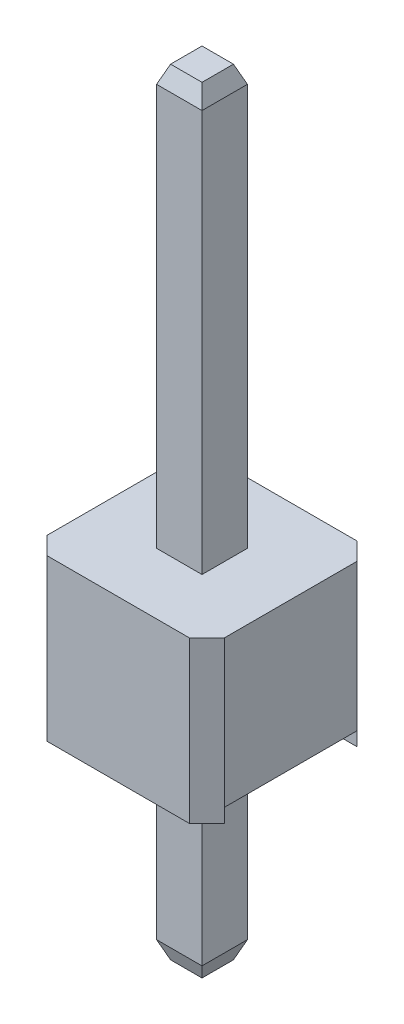
SolidWorks part; units mm, degrees
ref_plane "Front Plane" through (0, 0, 0) normal (0, 0, 1) x (1, 0, 0)
ref_plane "Top Plane" through (0, 0, 0) normal (0, 1, 0) x (1, 0, 0)
ref_plane "Right Plane" through (0, 0, 0) normal (1, 0, 0) x (0, 0, -1)
sketch "Sketch1" plane through (0, 0, 0) normal (0, 1, 0) x (1, 0, 0)
  line L1 (0, 0) -> (0.65, 0)
  line L2 (0, 0) -> (0, -0.65)
  line L3 (0, -0.65) -> (0.65, -0.65)
  line L4 (0.65, 0) -> (0.65, -0.65)
  dimension "D1" = 0.65
  dimension "D2" = 0.65
extrude "Boss-Extrude1" add sketch "Sketch1" along normal blind 11.3
chamfer "Chamfer1" distance 0.25 distance2 0.1 4 edges at (0.325, 11.3, 0) (0.65, 11.3, 0.325) (0.325, 11.3, 0.65) (0, 11.3, 0.325) first distance on face at (0.325, 5.65, 0) first distance on face at (0.65, 5.65, 0.325) first distance on face at (0.325, 5.65, 0.65) first distance on face at (0, 5.65, 0.325)
chamfer "Chamfer2" distance 0.1 distance2 0.25 4 edges at (0.325, 0, 0.65) (0.65, 0, 0.325) (0.325, 0, 0) (0, 0, 0.325) first distance on face at (0.325, 0, 0.325)
ref_plane "Plane1" through (0, 3, 0) normal (0, -1, 0) x (-1, 0, 0)
sketch "Sketch2" plane through (0, 3, 0) normal (0, -1, 0) x (-1, 0, 0)
  line L0 (-0.65, -0.325) -> (0, -0.325) construction
  line L5 (-1.595, 0.875) -> (0.945, 0.875)
  line L6 (-1.595, 0.875) -> (-1.595, -1.525)
  line L7 (-1.595, -1.525) -> (0.945, -1.525)
  line L8 (0.945, 0.875) -> (0.945, -1.525)
  line L9 (-0.65, -0.65) -> (-0.65, 0) construction
  line L10 (0, 0) -> (0, -0.65) construction
  line L11 (-0.325, -0.325) -> (-2.865, -0.325) construction
  point P10 (-1.595, -0.325)
  dimension "D1" = 2.4
  dimension "D2" = 1.2
  dimension "D3" = 2.54
  dimension "D4" = 1.27
extrude "Boss-Extrude2" add sketch "Sketch2" against normal blind 2.3
chamfer "Chamfer3" distance 0.25 angle 45 4 edges at (-0.945, 4.15, -0.875) (-0.945, 4.15, 1.525) (1.595, 4.15, 1.525) (1.595, 4.15, -0.875)
sketch "Sketch6" plane through (1.595, 0, 0) normal (1, 0, 0) x (0, 0, -1)
  line L0 (-1.527, 3) -> (1.527, 3) construction
  line L1 (-1.275, 3) -> (0.625, 3)
  line L2 (-1.275, 3) -> (-1.275, 3.2)
  line L3 (-1.275, 3.2) -> (0.625, 3.2)
  line L4 (0.625, 3) -> (0.625, 3.2)
  line L5 (-1.275, 5.3) -> (-1.275, 3) construction
  line L6 (0.625, 3) -> (0.625, 5.3) construction
  dimension "D1" = 0.2
extrude "Cut-Extrude5" cut sketch "Sketch6" against normal blind 6
sketch "Sketch7" plane through (0, 3.2, 0) normal (0, -1, 0) x (1, 0, 0)
  line L1 (0, 0) -> (0.65, 0)
  line L2 (0, 0) -> (0, 0.65)
  line L3 (0, 0.65) -> (0.65, 0.65)
  line L4 (0.65, 0) -> (0.65, 0.65)
extrude "Boss-Extrude4" add sketch "Sketch7" along normal blind 3
chamfer "Chamfer5" distance 0.25 distance2 0.1 4 edges at (0.325, 0.2, 0.65) (0.65, 0.2, 0.325) (0.325, 0.2, 0) (0, 0.2, 0.325) first distance on face at (0.325, 1.7, 0.65) first distance on face at (0.65, 1.7, 0.325) first distance on face at (0.325, 1.7, 0) first distance on face at (0, 1.7, 0.325)
